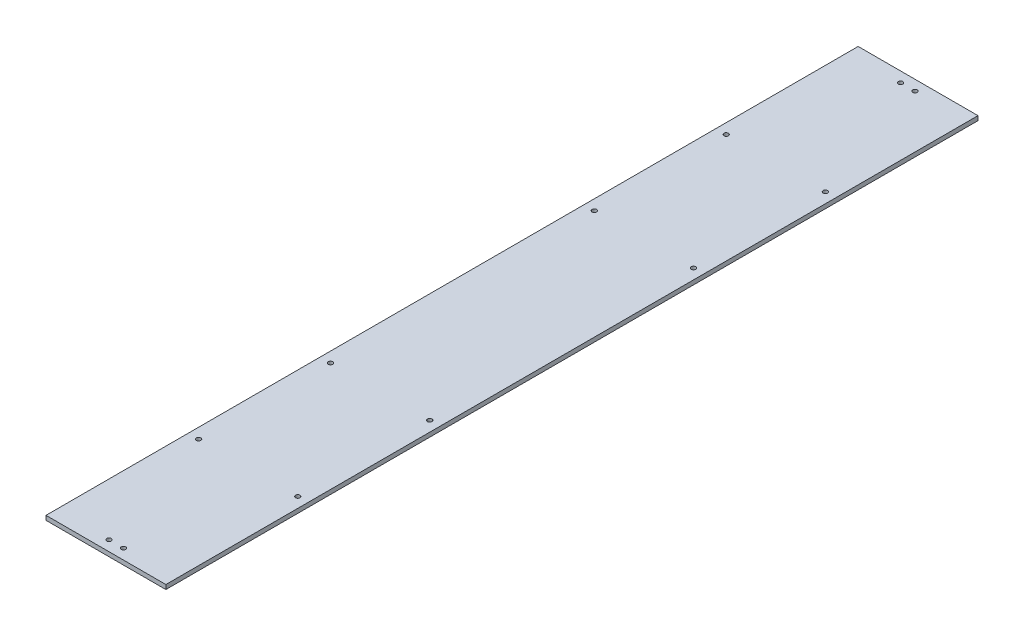
SolidWorks part; units mm, degrees
ref_plane "Front Plane" through (0, 0, 0) normal (0, 0, 1) x (1, 0, 0)
ref_plane "Top Plane" through (0, 0, 0) normal (0, 1, 0) x (1, 0, 0)
ref_plane "Right Plane" through (0, 0, 0) normal (1, 0, 0) x (0, 0, -1)
sketch "Sketch1" plane through (0, 0, 0) normal (0, 1, 0) x (1, 0, 0)
  line L0 (-43.575, 0) -> (43.575, 0) construction
  line L1 (-43.575, 295.275) -> (43.575, 295.275)
  line L2 (-43.575, 295.275) -> (-43.575, -295.275)
  line L3 (-43.575, -295.275) -> (43.575, -295.275)
  line L4 (43.575, 295.275) -> (43.575, -295.275)
  line L5 (-43.575, 295.275) -> (43.575, -295.275) construction
  line L6 (-43.575, -295.275) -> (43.575, 295.275) construction
  line L11 (0, 295.275) -> (0, -295.275) construction
  line L13 (-36.075, 287.775) -> (36.075, 287.775) construction
  line L14 (-36.075, 287.775) -> (-36.075, -287.775) construction
  line L15 (-36.075, -287.775) -> (36.075, -287.775) construction
  line L16 (36.075, 287.775) -> (36.075, -287.775) construction
  line L17 (-36.075, 287.775) -> (36.075, -287.775) construction
  line L18 (-36.075, -287.775) -> (36.075, 287.775) construction
  circle A0 centre (-5.275, 287.775) radius 1.65
  circle A1 centre (-36.075, 191.8483) radius 1.65
  circle A2 centre (-36.075, 95.9217) radius 1.65
  circle A3 centre (36.075, 95.9217) radius 1.65
  circle A4 centre (36.075, 191.8483) radius 1.65
  circle A5 centre (5.275, 287.775) radius 1.65
  circle A6 centre (5.275, -287.775) radius 1.65
  circle A7 centre (36.075, -191.8483) radius 1.65
  circle A8 centre (36.075, -95.9217) radius 1.65
  circle A9 centre (-36.075, -95.9217) radius 1.65
  circle A10 centre (-36.075, -191.8483) radius 1.65
  circle A11 centre (-5.275, -287.775) radius 1.65
  point P0 (0, 0)
  point P6 (0, 0)
  point P11 (0, 0)
  dimension "D5" = 3.3
  dimension "D6" = 3.3
  dimension "D7" = 3.3
  dimension "D3" = 87.15
  dimension "D1" = 7.5
  dimension "D2" = 7.5
  dimension "D4" = 590.55
  dimension "D8" = 30.8
  dimension "D9" = 95.9267
  dimension "D10" = 95.9267
  dimension "D11" = 95.9217
extrude "Boss-Extrude1" add sketch "Sketch1" along normal blind 3.175
equation "\"D6@Sketch1\"=\"D5@Sketch1\""
equation "\"D7@Sketch1\"=\"D6@Sketch1\""
equation "\"D10@Sketch1\"=\"D9@Sketch1\""
